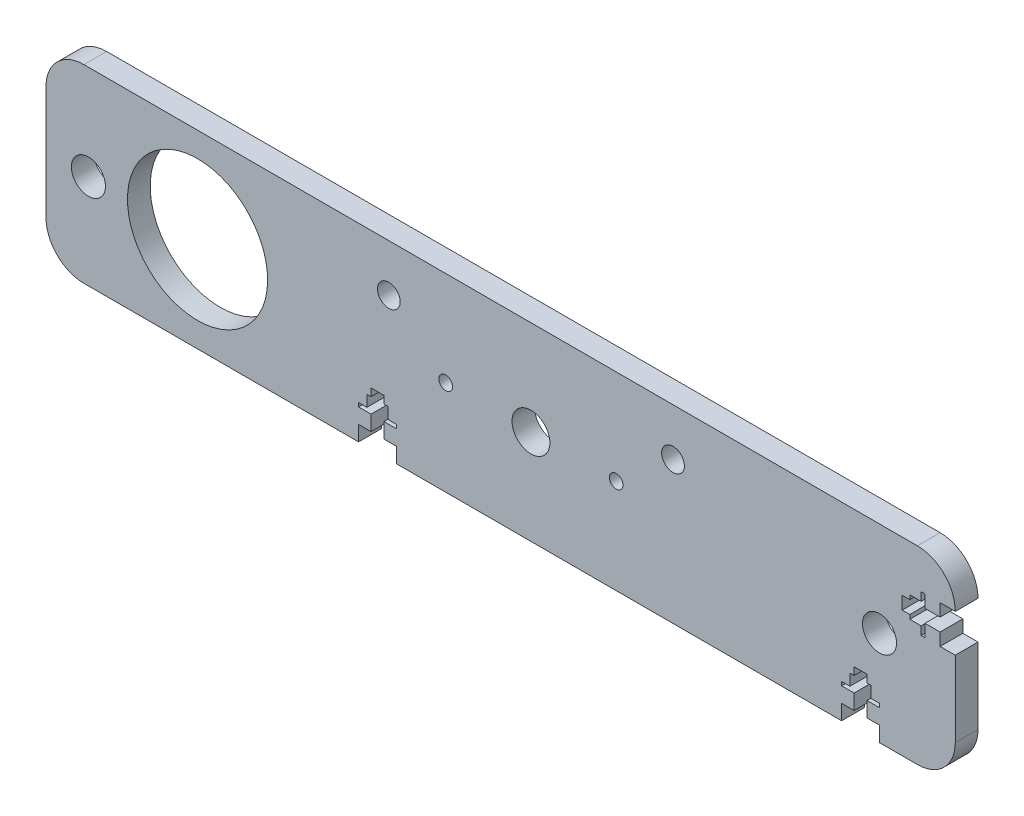
SolidWorks part; units mm, degrees
material "Balsa"
ref_plane "Plano frontal" through (0, 0, 0) normal (0, 0, 1) x (1, 0, 0)
ref_plane "Plano superior" through (0, 0, 0) normal (0, 1, 0) x (1, 0, 0)
ref_plane "Plano direito" through (0, 0, 0) normal (1, 0, 0) x (0, 0, -1)
sketch "Esboço1" plane through (0, 0, 0) normal (0, 0, 1) x (1, 0, 0)
  line L0 (100, -25) -> (100, -21)
  line L1 (-110, -25) -> (-37.5, -25)
  line L2 (-120, -15) -> (-120, 15)
  line L3 (-110, 25) -> (110, 25)
  line L4 (120, 5) -> (120, -15)
  line L5 (-120, -25) -> (120, 25) construction
  line L6 (-120, 25) -> (120, -24.5772) construction
  line L7 (-80, 18.5) -> (-80, 25) construction
  line L8 (8, 25) -> (8, 0) construction
  line L9 (-104.31, 0) -> (-104.31, 1.5)
  line L10 (-29.5, 12.5) -> (45.5, 12.5) construction
  line L11 (-14.5, 0) -> (30.5, 0) construction
  line L12 (100, -21) -> (96.7, -21)
  line L13 (90, -21) -> (90, -25)
  line L14 (-37.5, -25) -> (-37.5, -21)
  line L15 (-37.5, -21) -> (-34.2, -21)
  line L16 (-27.5, -21) -> (-27.5, -25)
  line L17 (-27.5, -25) -> (90, -25)
  line L18 (-32.5, -25) -> (-32.5, -13.0244) construction
  line L19 (-34.2, -21) -> (-34.2, -17)
  line L20 (-34.2, -17) -> (-37.5, -17)
  line L21 (-35.3, -16) -> (-35.3, -13)
  line L22 (-35.3, -13) -> (-34.2, -13)
  line L23 (-37.5, -25) -> (-27.5, -25) construction
  line L24 (-34.2, -13) -> (-34.2, -11)
  line L25 (-34.2, -11) -> (-30.8, -11)
  line L26 (-35.3, -16) -> (-37.5, -16)
  line L27 (-37.5, -16) -> (-37.5, -17)
  line L28 (-27.5, -16) -> (-27.5, -17)
  line L29 (-29.7, -16) -> (-27.5, -16)
  line L30 (-30.8, -13) -> (-30.8, -11)
  line L31 (-29.7, -13) -> (-30.8, -13)
  line L32 (-29.7, -16) -> (-29.7, -13)
  line L33 (-30.8, -17) -> (-27.5, -17)
  line L34 (-30.8, -21) -> (-30.8, -17)
  line L35 (-27.5, -21) -> (-30.8, -21)
  line L36 (100, -16) -> (100, -17)
  line L37 (90, -16) -> (90, -17)
  line L38 (96.7, -17) -> (100, -17)
  line L39 (93.3, -17) -> (90, -17)
  line L40 (96.7, -13) -> (96.7, -11)
  line L41 (97.8, -13) -> (96.7, -13)
  line L42 (93.3, -13) -> (93.3, -11)
  line L43 (93.3, -11) -> (96.7, -11)
  line L44 (93.3, -21) -> (93.3, -17)
  line L45 (95, -25) -> (95, -21) construction
  line L46 (92.2, -16) -> (92.2, -13)
  line L47 (96.7, -21) -> (96.7, -17)
  line L48 (97.8, -16) -> (100, -16)
  line L49 (92.2, -16) -> (90, -16)
  line L50 (92.2, -13) -> (93.3, -13)
  line L51 (97.8, -16) -> (97.8, -13)
  line L52 (93.3, -21) -> (90, -21)
  line L53 (90, -25) -> (100, -25) construction
  line L54 (110, -25) -> (100, -25)
  line L55 (120, 15) -> (116, 15)
  line L56 (116, 15) -> (116, 11.7)
  line L57 (116, 5) -> (120, 5)
  line L58 (111, 15) -> (112, 15)
  line L59 (111, 5) -> (112, 5)
  line L60 (112, 11.7) -> (112, 15)
  line L61 (112, 8.3) -> (112, 5)
  line L62 (108, 11.7) -> (106, 11.7)
  line L63 (108, 12.8) -> (108, 11.7)
  line L64 (108, 8.3) -> (106, 8.3)
  line L65 (106, 8.3) -> (106, 11.7)
  line L66 (116, 8.3) -> (112, 8.3)
  line L67 (111, 7.2) -> (108, 7.2)
  line L68 (116, 11.7) -> (112, 11.7)
  line L69 (111, 12.8) -> (111, 15)
  line L70 (111, 7.2) -> (111, 5)
  line L71 (108, 7.2) -> (108, 8.3)
  line L72 (111, 12.8) -> (108, 12.8)
  line L73 (116, 8.3) -> (116, 5)
  circle A0 centre (-80, 0) radius 18.5
  circle A1 centre (100, 0) radius 4.5
  arc A2 (120, -15) -> (110, -25) centre (110, -15) cw
  arc A3 (110, 25) -> (120, 15) centre (110, 15) cw
  arc A4 (-120, 15) -> (-110, 25) centre (-110, 15) cw
  arc A5 (-110, -25) -> (-120, -15) centre (-110, -15) cw
  circle A6 centre (8, 0) radius 5
  circle A7 centre (-108.81, 0) radius 4.5
  circle A8 centre (-14.5, 0) radius 1.8
  circle A9 centre (30.5, 0) radius 1.8
  circle A10 centre (-29.5, 12.5) radius 3
  circle A11 centre (45.5, 12.5) radius 3
  point P0 (0, 0)
  point P34 (8, 12.5)
  point P35 (8, 0)
  point P42 (8, 12.5)
  point P60 (-32.5, -25)
  point P67 (-32.5, -11)
  point P84 (94.8463, -8.5)
  point P89 (95, -25)
  point P91 (0, 0)
  point P95 (0, 0)
  point P108 (103.5, 9.8463)
  point P112 (0, 0)
  point P113 (0, 0)
  point P114 (0, 0)
  point P115 (0, 0)
  point P116 (0, 0)
  point P117 (-17.5, -25)
  dimension "D3" = 37
  dimension "D5" = 9
  dimension "D6" = 10
  dimension "D9" = 28.81
  dimension "D10" = 75
  dimension "D11" = 6
  dimension "D12" = 3.6
  dimension "D14" = 10
  dimension "D1" = 240
  dimension "D2" = 50
  dimension "D4" = 180
  dimension "D7" = 4
  dimension "D8" = 10
  dimension "D13" = 45
  dimension "D15" = 4
  dimension "D16" = 10
  dimension "D17" = 4
  dimension "D18" = 4
  dimension "D19" = 4
  dimension "D20" = 5.6
  dimension "D21" = 3.4
  dimension "D22" = 2
  dimension "D23" = 1
  dimension "D24" = 10
  dimension "D25" = 4
  dimension "D26" = 5.6
  dimension "D27" = 25
  dimension "D28" = 2
  dimension "D29" = 4
  dimension "D30" = 1
  dimension "D31" = 10
  dimension "D32" = 2
  dimension "D33" = 8
  dimension "D34" = 4
  dimension "D35" = 127.5
  dimension "D36" = 3.4
  dimension "D37" = 25
extrude "Ressalto-extrusão1" add sketch "Esboço1" along normal blind 6 contours A5 L1 A3 L3 A4 L2 A11 A10 A9 A8 A6 A1 A0 A7 region at (102.4515, -23, 0)
